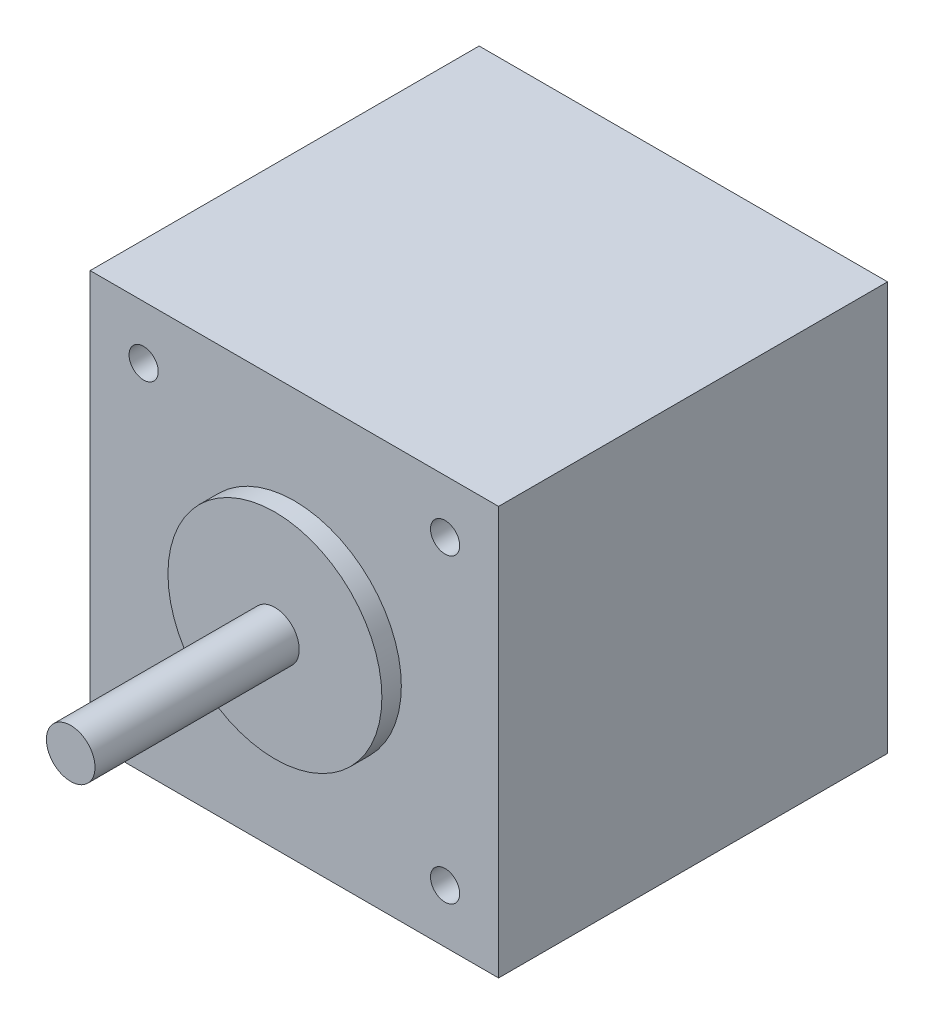
SolidWorks part; units mm, degrees
ref_plane "Спереди" through (0, 0, 0) normal (0, 0, 1) x (1, 0, 0)
ref_plane "Сверху" through (0, 0, 0) normal (0, 1, 0) x (1, 0, 0)
ref_plane "Справа" through (0, 0, 0) normal (1, 0, 0) x (0, 0, -1)
other "Configuration Table"
sketch "Эскиз1" plane through (0, 0, 0) normal (0, 0, 1) x (1, 0, 0)
  line L1 (-21, -21) -> (21, -21)
  line L2 (-21, -21) -> (-21, 21)
  line L3 (-21, 21) -> (21, 21)
  line L4 (21, -21) -> (21, 21)
  line L5 (-21, -21) -> (21, 21) construction
  line L6 (-21, 21) -> (21, -21) construction
  point P0 (0, 0)
  dimension "D1" = 42
  dimension "D2" = 42
extrude "Корпус" add sketch "Эскиз1" along normal blind 40
sketch "Эскиз2" plane through (0, 0, 0) normal (0, 0, 1) x (1, 0, 0)
  circle A0 centre (0, 0) radius 2.5
extrude "Вал_ПРЕДВ" add sketch "Эскиз2" along normal blind 63
sketch "Эскиз3" plane through (0, 0, 0) normal (0, 0, 1) x (1, 0, 0)
  circle A0 centre (0, 0) radius 11
  dimension "D1" = 22
extrude "Буртик_ПРЕДВ" add sketch "Эскиз3" along normal blind 42
sketch "Эскиз4" plane through (0, 0, 0) normal (0, 0, 1) x (1, 0, 0)
  circle A0 centre (-15.5, -15.5) radius 1.5
  circle A1 centre (-15.5, 15.5) radius 1.5
  circle A2 centre (15.5, -15.5) radius 1.5
  circle A3 centre (15.5, 15.5) radius 1.5
  dimension "D1" = 3
  dimension "D2" = 3
  dimension "D3" = 3
  dimension "D4" = 3
extrude "Крепеж_М3_ПРЕДВ" cut sketch "Эскиз4" against normal blind 4.5 from offset 40
equation "\"Мотор X ширина корпуса\"= 42.3"
equation "\"Мотор X высота корпуса\"= 42.3"
equation "\"Мотор X длина корпуса\"= 40"
equation "\"Мотор X вылет вала\"= 19.8"
equation "\"Мотор Y ширина корпуса\"= 42.3"
equation "\"Мотор Y высота корпуса\"= 42.3"
equation "\"Мотор Y длина корпуса\"= 48"
equation "\"Мотор Y вылет вала\"= 30"
equation "\"Мотор Z ширина корпуса\"= 42"
equation "\"Мотор Z высота корпуса\"= 42"
equation "\"Мотор Z длина корпуса\"= 40"
equation "\"Мотор Z вылет вала\"= 23"
equation "\"Мотор диаметр вала ПРЕДВ\"= 5"
equation "\"Мотор шаг крепления ПРЕДВ\"= 31"
equation "\"Мотор диаметр отверстий ПРЕДВ\"= 3"
equation "\"Мотор глубина отверстий ПРЕДВ\"= 4.5"
equation "\"Мотор диаметр буртика ПРЕДВ\"= 22"
equation "\"Мотор высота буртика ПРЕДВ\"= 2"
equation "\"Мотор диаметр шкива ПРЕДВ\"= 16"
equation "\"Мотор длина шкива ПРЕДВ\"= 12"
equation "\"Мотор отступ шкива ПРЕДВ\"= 5"
equation "\"Мотор X шаг градусов\"= 1.8"
equation "\"Мотор X ток А\"= 1.5"
equation "\"Мотор X сопротивление Ом\"= 1.3"
equation "\"Мотор X индуктивность мГн\"= 2"
equation "\"Мотор Y шаг градусов\"= 1.8"
equation "\"Мотор Y ток А\"= 2.2"
equation "\"Мотор Y сопротивление Ом\"= 0.9"
equation "\"Мотор Y индуктивность мГн\"= 2"
equation "\"Мотор Z шаг градусов\"= 1.8"
equation "\"Мотор Z ток А\"= 1"
equation "\"Мотор Z сопротивление Ом\"= 4"
equation "\"Мотор Z индуктивность мГн\"= 8"
equation "\"Мотор Y диаметр ротора\"= 25.78"
equation "\"D1@Эскиз1\" = \"Мотор Z ширина корпуса\""
equation "\"D2@Эскиз1\" = \"Мотор Z высота корпуса\""
equation "\"D1@Корпус\" = \"Мотор Z длина корпуса\""
equation "\"D1@Эскиз2\" = \"Мотор диаметр вала ПРЕДВ\""
equation "\"D1@Вал_ПРЕДВ\" = \"Мотор Z длина корпуса\" + \"Мотор Z вылет вала\""
equation "\"D1@Эскиз3\" = \"Мотор диаметр буртика ПРЕДВ\""
equation "\"D1@Буртик_ПРЕДВ\" = \"Мотор Z длина корпуса\" + \"Мотор высота буртика ПРЕДВ\""
equation "\"D1@Эскиз4\" = \"Мотор диаметр отверстий ПРЕДВ\""
equation "\"D2@Эскиз4\" = \"Мотор диаметр отверстий ПРЕДВ\""
equation "\"D3@Эскиз4\" = \"Мотор диаметр отверстий ПРЕДВ\""
equation "\"D4@Эскиз4\" = \"Мотор диаметр отверстий ПРЕДВ\""
equation "\"D1@Крепеж_М3_ПРЕДВ\" = \"Мотор глубина отверстий ПРЕДВ\""
equation "\"D19@Крепеж_М3_ПРЕДВ\" = \"Мотор Z длина корпуса\""
equation "\"Ширина груза\"= 160"
equation "\"Глубина груза\"= 240"
equation "\"Высота груза\"= 160"
equation "\"Ширина ячейки\"= \"Ширина груза\" + 10"
equation "\"Глубина ячейки\"= \"Глубина груза\" + 10"
equation "\"Высота ячейки\"= \"Высота груза\" + 10 + 13"
equation "\"Колво ячеек ширина\"= 2"
equation "\"Колво ячеек высота\"= 2"
equation "\"Толщина стенки\" = \"Толщина тонких панелей\""
equation "\"Крепление дверцы\"= 5 "
equation "\"Ширина рейки\"= \"Толщина шестерни\""
equation "\"Высота рейки\"= 20"
equation "\"Высота пола\" = 2*\"Толщина тонких панелей\""
equation "\"Колво полозьев\"= 5"
equation "\"Отступ рейки\"= 20"
equation "\"Глубина каретки\"= \"Глубина ячейки\" + 30 + \"Мотор Y высота корпуса\" + 20"
equation "\"Отступ шпильки\"= 26"
equation "\"Диаметр шпильки\"= 5"
equation "\"Длинна шпильки\" = (\"Высота ячейки\"+\"Толщина горизонтальных плит\"+\"Высота пола\")*\"Колво ячеек высота\"+2*(\"Толщина горизонтальных плит\"+\"Отступ рейки\")"
equation "\"Ширина пластины\"= 50  "
equation "\"Высота зона выгрузки\"= \"Высота ячейки\" * 2 + \"Толщина стенки\" * 2"
equation "\"Колво выгрузки\"= 1"
equation "\"Отступ крепления мотора фиксации\" = (\"Ширина пластины\"+20-\"Толщина вертикальных стенок\")/2"
equation "\"Диаметр оси\"= 10"
equation "\"Диаметр ролика\"= 20"
equation "\"Колво роликов\"= 10"
equation "\"Шаг роликов\"= \"Диаметр ролика\" + 20"
equation "\"Ширина ячейки выгрузки\" = \"Ширина ячейки\"+\"Толщина вертикальных стенок\"+2*\"Отступ крепления мотора фиксации\""
equation "\"Длинна рейки\" = (\"Ширина ячейки\"+\"Толщина вертикальных стенок\"+\"Крепление дверцы\")*\"Колво ячеек ширина\"+\"Ширина ячейки выгрузки\"*\"Колво выгрузки\"+\"Толщина вертикальных стенок\"+2*\"Отступ крепления мотора фиксации\"-\"Крепление дверцы\"*\"Колво ячеек ширина\""
equation "\"Толщина тонких панелей\" = 6"
equation "\"Толщина вертикальных стенок\" = 6"
equation "\"Толщина горизонтальных плит\" = 6"
equation "\"Базовая высота корпуса\"= (\"Высота ячейки\"+\"Толщина тонких панелей\"+\"Высота пола\")*\"Колво ячеек высота\"+6*\"Толщина тонких панелей\"+\"Мотор X ширина корпуса\"+\"Мотор Y ширина корпуса\"+75"
equation "\"Высота корпуса\"= (\"Высота ячейки\"+\"Толщина горизонтальных плит\"+\"Высота пола\")*\"Колво ячеек высота\"+2*\"Толщина горизонтальных плит\"+4*\"Толщина тонких панелей\"+\"Мотор X ширина корпуса\"+\"Мотор Y ширина корпуса\"+75"
equation "\"Смещение центра корпуса\"= (\"Высота корпуса\"-\"Базовая высота корпуса\")/2-(\"Толщина горизонтальных плит\"-\"Толщина тонких панелей\")"
equation "\"Отметка пола\"= -\"Базовая высота корпуса\"/2+\"Толщина тонких панелей\""
equation "\"Отметка потолка\"= \"Отметка пола\"+\"Высота корпуса\"-2*\"Толщина горизонтальных плит\""
equation "\"Отметка верхней полки\"= \"Отметка потолка\"-(28+\"Толщина тонких панелей\")-\"Высота ячейки\"-\"Высота пола\""
equation "\"Отметка нижней полки\"= \"Отметка верхней полки\"-\"Высота ячейки\"-\"Высота пола\"-\"Толщина горизонтальных плит\""
equation "\"Толщина шестерни\"= 10"
